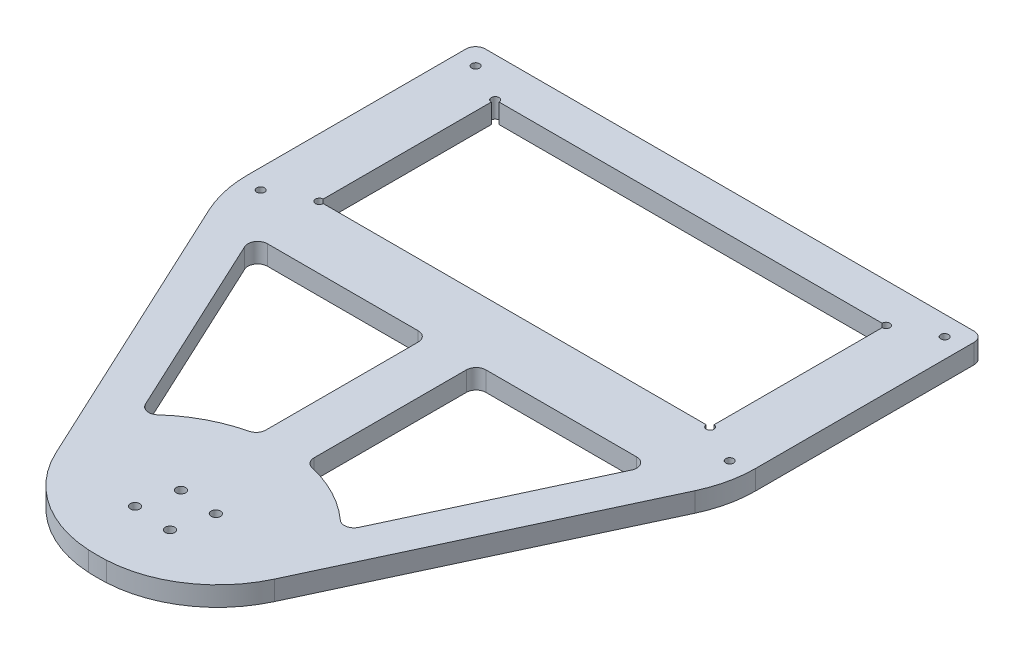
SolidWorks part; units mm, degrees
ref_plane "Front Plane" through (0, 0, 0) normal (0, 0, 1) x (1, 0, 0)
ref_plane "Top Plane" through (0, 0, 0) normal (0, 1, 0) x (1, 0, 0)
ref_plane "Right Plane" through (0, 0, 0) normal (1, 0, 0) x (0, 0, -1)
sketch "Sketch1" plane through (0, 0, 0) normal (0, 1, 0) x (1, 0, 0)
  line L0 (-82.55, -41.275) -> (-28.8775, -156.3761)
  line L1 (-82.55, 41.275) -> (82.55, 41.275)
  line L2 (-82.55, 41.275) -> (-82.55, -41.275)
  line L3 (-82.55, -41.275) -> (82.55, -41.275)
  line L4 (82.55, 41.275) -> (82.55, -41.275)
  line L5 (-82.55, 41.275) -> (82.55, -41.275) construction
  line L6 (-82.55, -41.275) -> (82.55, 41.275) construction
  line L7 (82.55, -41.275) -> (28.8775, -156.3761)
  arc A0 (-28.8775, -156.3761) -> (28.8775, -156.3761) centre (0, -107.0586) ccw
  point P0 (0, 0)
  dimension "D7" = 57.15
  dimension "D1" = 165.1
  dimension "D2" = 82.55
  dimension "D3" = 65
  dimension "D4" = 65
  dimension "D5" = 127
  dimension "D6" = 127
extrude "Boss-Extrude2" add sketch "Sketch1" along normal blind 6.35 contours L0 A0 L7 L3 | L4 L1 L2 L3 region at (0, 0, 91.2149) region at (0, 0, 0)
sketch "Sketch4" plane through (0, 6.35, 0) normal (0, 1, 0) x (1, 0, 0)
  line L0 (0, -164.2086) -> (0, -138.8086) construction
  line L1 (-7.6031, -144.3326) -> (7.6031, -133.2846)
  line L2 (-4.7029, -132.3357) -> (4.7029, -145.2816)
  arc A1 (-28.8775, -156.3761) -> (28.8775, -156.3761) centre (0, -107.0586) ccw construction
  circle A7 centre (-4.7029, -132.3357) radius 1.524
  circle A8 centre (7.6031, -133.2846) radius 1.524
  circle A9 centre (4.7029, -145.2816) radius 1.524
  circle A10 centre (-7.6031, -144.3326) radius 1.524
  point P6 (0, -138.8086)
  point P8 (0, -138.8086)
  dimension "D1" = 18.796
  dimension "D2" = 16.002
  dimension "D4" = 3.048
  dimension "D3" = 25.4
  dimension "D5" = 36
extrude "Cut-Extrude5" cut sketch "Sketch4" against normal through all both and the other way through all contours A9 | A10 | A8 | A7 region at (-6.0224, 6.35, 131.6634) region at (7.1455, 6.35, 131.8762) region at (5.3752, 6.35, 143.9621) region at (-6.1947, 6.35, 143.875)
sketch "Sketch5" plane through (0, 6.35, 0) normal (0, 1, 0) x (1, 0, 0)
  line L0 (-82.55, 41.275) -> (-82.55, -41.275) construction
  line L1 (-82.55, 41.275) -> (82.55, 41.275) construction
  circle A0 centre (-76.2, 34.925) radius 1.27
  circle A1 centre (-76.2, -34.925) radius 1.27
  point P4 (0, 0)
  point P11 (-72.366, -51.9371)
  dimension "D1" = 2.54
  dimension "D4" = 2.54
  dimension "D6" = 76.2
  dimension "D2" = 6.35
  dimension "D3" = 6.35
  dimension "D5" = 6.35
extrude "Cut-Extrude7" cut sketch "Sketch5" against normal through all
mirror "Mirror2" about plane through (0, 0, 0) normal (1, 0, 0) of "Cut-Extrude7"
fillet "Fillet4" radius 38.1 4 edges at (82.55, 3.175, 41.275) (28.8775, 3.175, 156.3761) (-28.8775, 3.175, 156.3761) (-82.55, 3.175, 41.275)
sketch "Sketch7" plane through (0, 6.35, 0) normal (0, 1, 0) x (1, 0, 0)
  line L0 (-82.55, 41.275) -> (82.55, 41.275) construction
  line L1 (-63.5, 28.575) -> (63.5, 28.575)
  line L2 (-63.5, 28.575) -> (-63.5, -28.575)
  line L3 (-63.5, -28.575) -> (63.5, -28.575)
  line L4 (63.5, 28.575) -> (63.5, -28.575)
  line L5 (-63.5, 28.575) -> (63.5, -28.575) construction
  line L6 (-63.5, -28.575) -> (63.5, 28.575) construction
  line L7 (82.55, 41.275) -> (82.55, -32.8284) construction
  circle A0 centre (-63.5, 28.575) radius 1.27
  circle A1 centre (-63.5, -28.575) radius 1.27
  circle A2 centre (63.5, -28.575) radius 1.27
  circle A3 centre (63.5, 28.575) radius 1.27
  point P0 (0, 0)
  dimension "D3" = 2.54
  dimension "D1" = 12.7
  dimension "D2" = 19.05
extrude "Cut-Extrude9" cut sketch "Sketch7" against normal through all both and the other way through all contours A3 L1 A0 L2 A1 L3 A2 L4 | L1 A0 L2 | L2 A0 L1 | L2 A1 L3 | L3 A1 L2 | L3 A2 L4 | L4 A2 L3 | L4 A3 L1 | L4 L3 L2 L1 region at (-63.6797, 6.35, -28.7547) region at (-62.961, 6.35, -28.036) region at (0, 6.35, 0) region at (63.6797, 6.35, -28.7547) region at (-62.961, 6.35, 28.036) region at (-63.6797, 6.35, 28.7547) region at (63.6797, 6.35, 28.7547) region at (62.961, 6.35, 28.036)
sketch "Sketch8" plane through (0, 6.35, 0) normal (0, 1, 0) x (1, 0, 0)
  line L0 (-64.9674, -48.9302) -> (-32.7639, -117.9908)
  line L7 (64.9674, -48.9302) -> (32.7639, -117.9908)
  line L8 (78.9803, -48.9302) -> (35.4944, -142.186) construction
  line L9 (-78.9803, -48.9302) -> (-35.4944, -142.186) construction
  line L10 (-64.9674, -48.9302) -> (64.9674, -48.9302)
  line L12 (-7.8174, -48.9302) -> (-7.8174, -104.1841)
  line L13 (7.8174, -48.9302) -> (7.8174, -104.1841)
  arc A1 (-32.7639, -117.9908) -> (32.7639, -117.9908) centre (0, -147.7492) cw
  dimension "D3" = 44.261
  dimension "D1" = 76.2
  dimension "D2" = 76.2
  dimension "D4" = 12.7
  dimension "D5" = 12.7
  dimension "D6" = 57.15
  dimension "D7" = 57.15
extrude "Cut-Extrude10" cut sketch "Sketch8" against normal through all both and the other way through all contours L0 A1 L12 L10 | L13 A1 L7 L10 region at (-30.4156, 6.35, 76.1401) region at (30.4156, 6.35, 76.1401)
fillet "Fillet5" radius 3.175 10 edges at (64.9674, 3.175, 48.9302) (32.7639, 3.175, 117.9908) (7.8174, 3.175, 104.1841) (7.8174, 3.175, 48.9302) (-7.8174, 3.175, 48.9302) (-7.8174, 3.175, 104.1841) (-32.7639, 3.175, 117.9908) (-64.9674, 3.175, 48.9302) (-82.55, 3.175, -41.275) (82.55, 3.175, -41.275)
